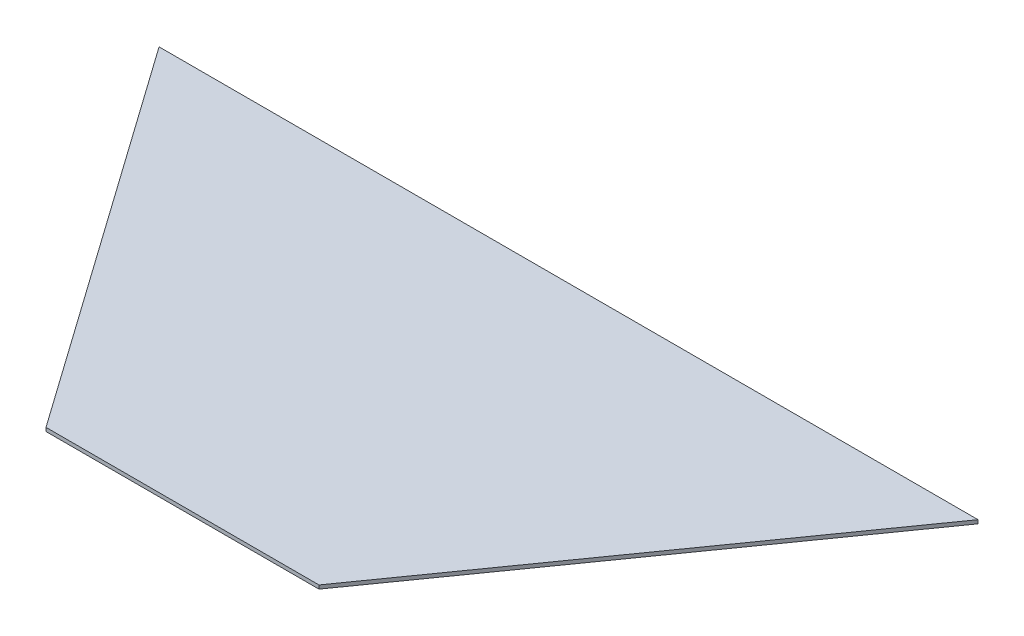
SolidWorks part; units mm, degrees
ref_plane "Front Plane" through (0, 0, 0) normal (0, 0, 1) x (1, 0, 0)
ref_plane "Top Plane" through (0, 0, 0) normal (0, 1, 0) x (1, 0, 0)
ref_plane "Right Plane" through (0, 0, 0) normal (1, 0, 0) x (0, 0, -1)
sketch "Sketch1" plane through (0, 0, 0) normal (0, 1, 0) x (1, 0, 0)
  line L0 (-168.1105, 158.4961) -> (-56.0368, 0)
  line L1 (168.1105, 158.4961) -> (-168.1105, 158.4961)
  line L3 (56.0368, 0) -> (-56.0368, 0)
  line L5 (168.1105, 158.4961) -> (56.0368, 0)
  line L6 (0, 0) -> (0, 158.4961) construction
  point P9 (0, 158.4961)
  dimension "Base" = 112.0737
  dimension "D1" = 336.2211
  dimension "D2" = 158.4961
extrude "Boss-Extrude1" add sketch "Sketch1" along normal blind 1.5
equation "\"base\" = \"width\" / 3"
equation "\"Base@Sketch1\"= \"base\""
equation "\"height\"= 60"
equation "\"angle\"= 45deg"
equation "\"width\"= 13.23705in"
equation "\"D1@Sketch1\"=\"width\""
equation "\"D2@Sketch1\"=(\"width\"-\"base\")/2/sin(\"angle\")"
